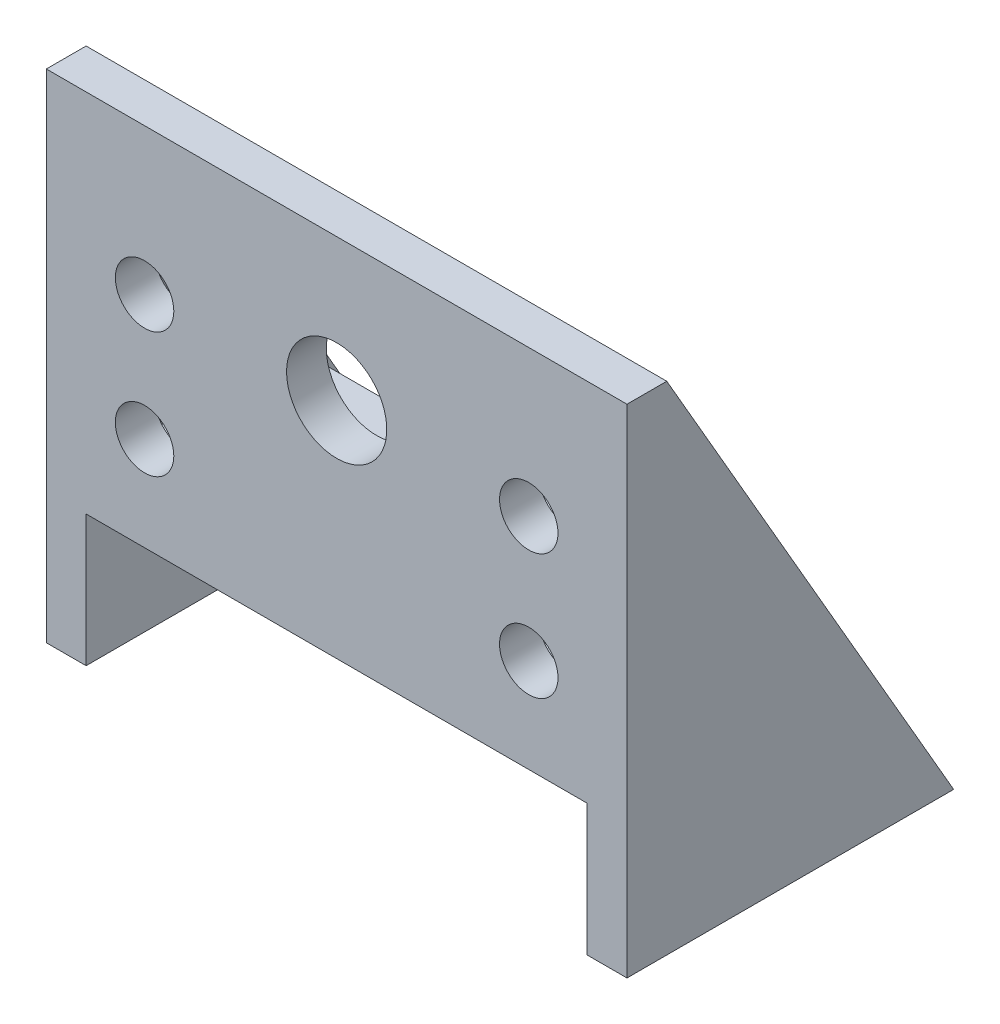
SolidWorks part; units mm, degrees
ref_plane "Alzado" through (0, 0, 0) normal (0, 0, 1) x (1, 0, 0)
ref_plane "Planta" through (0, 0, 0) normal (0, 1, 0) x (1, 0, 0)
ref_plane "Vista lateral" through (0, 0, 0) normal (1, 0, 0) x (0, 0, -1)
sketch "Croquis1" plane through (0, 0, 0) normal (0, 0, 1) x (1, 0, 0)
  line L1 (-37.7093, 8.066) -> (22.2907, 8.066)
  line L2 (-37.7093, 8.066) -> (-37.7093, -30.934)
  line L3 (-37.7093, -30.934) -> (22.2907, -30.934)
  line L4 (22.2907, 8.066) -> (22.2907, -30.934)
  circle A0 centre (-7.7093, -8.934) radius 6
  dimension "D3" = 12
  dimension "D5" = 30
  dimension "D1" = 60
  dimension "D2" = 39
  dimension "D4" = 17
extrude "Saliente-Extruir1" add sketch "Croquis1" along normal blind 4.7625
sketch "Croquis2" plane through (22.2907, 0, 0) normal (1, 0, 0) x (0, 0, -1)
  line L0 (-4.7625, 8.066) -> (-4.7625, -51.434)
  line L1 (-4.7625, -51.434) -> (34.3523, -51.434)
  line L2 (34.3523, -51.434) -> (0, 8.066)
  line L3 (0, 8.066) -> (-4.7625, 8.066)
  dimension "D1" = 59.5
  dimension "D2" = 60
extrude "Saliente-Extruir2" add sketch "Croquis2" along normal blind 4.7625
extrude "Saliente-Extruir3" add sketch "Croquis2<2>" against normal blind 4.7625 from surface starting at face at (-37.7093, -11.434, 2.3813)
sketch "Croquis2<2>" plane through (22.2907, 0, 0) normal (1, 0, 0) x (0, 0, -1) same geometry as "Croquis2"
sketch "Croquis4" plane through (0, 0, 4.7625) normal (0, 0, 1) x (1, 0, 0)
  line L0 (22.2907, -30.934) -> (22.2907, -51.434) construction
  line L1 (-37.7093, -30.934) -> (22.2907, -30.934)
  line L2 (-37.7093, -30.934) -> (-37.7093, -35.6965)
  line L3 (-37.7093, -35.6965) -> (22.2907, -35.6965)
  line L4 (22.2907, -30.934) -> (22.2907, -35.6965)
  dimension "D1" = 4.7625
extrude "Saliente-Extruir4" add sketch "Croquis4" against normal blind 25
sketch "Croquis5" plane through (0, 0, 4.7625) normal (0, 0, 1) x (1, 0, 0)
  line L0 (-42.4718, 8.066) -> (-42.4718, -51.434) construction
  line L1 (27.0532, 8.066) -> (-42.4718, 8.066) construction
  circle A0 centre (-30.7093, -9.434) radius 3.5
  circle A1 centre (15.2907, -9.434) radius 3.5
  circle A2 centre (15.2907, -24.434) radius 3.5
  circle A3 centre (-30.7093, -24.434) radius 3.5
  point P12 (0, 0)
  point P13 (0, 0)
  point P14 (0, 0)
  point P15 (0, 0)
  dimension "D1" = 7
  dimension "D2" = 11.7625
  dimension "D3" = 17.5
  dimension "D4" = 15
  dimension "D5" = 46
extrude "Cortar-Extruir1" cut sketch "Croquis5" against normal blind 10
